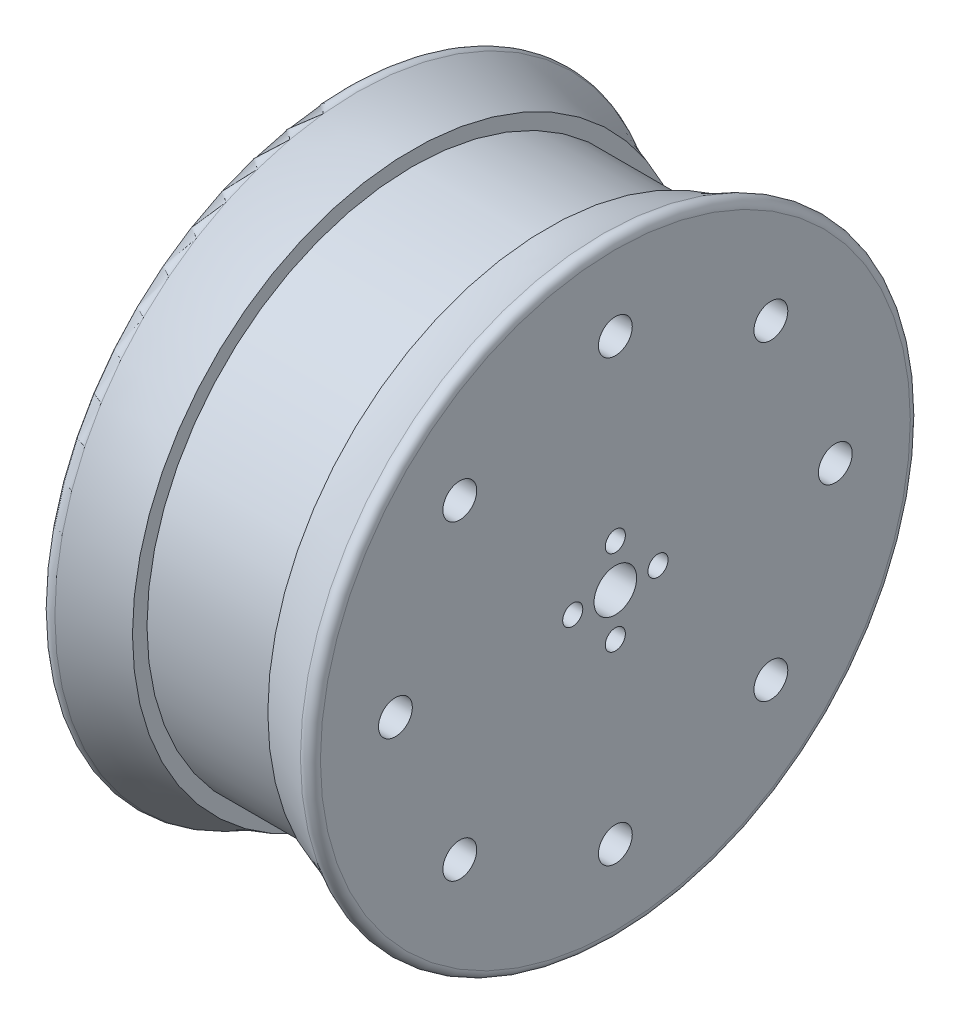
SolidWorks part; units mm, degrees
ref_plane "Front Plane" through (0, 0, 0) normal (0, 0, 1) x (1, 0, 0)
ref_plane "Top Plane" through (0, 0, 0) normal (0, 1, 0) x (1, 0, 0)
ref_plane "Right Plane" through (0, 0, 0) normal (1, 0, 0) x (0, 0, -1)
sketch "Wheel Arc" plane through (0, 0, 0) normal (0, 0, 1) x (1, 0, 0)
  line L0 (0, 0) -> (0, -98.425) construction
  line L1 (-25.4, 0) -> (25.4, 0)
  line L2 (-40.9053, 0) -> (38.2322, 0) construction
  line L3 (-25.4, 0) -> (-25.4, -58.1388)
  line L4 (25.4, 0) -> (25.4, -58.1388)
  line L5 (0, -50.8) -> (0, -49.8) construction
  line L6 (-12.7, -49.8) -> (12.7, -49.8)
  line L7 (-12.7, -49.8) -> (-12.7, -52.5246)
  line L8 (12.7, -49.8) -> (12.7, -52.5246)
  arc A0 (-25.4, -58.1388) -> (-12.7, -52.5246) centre (0, -98.425) cw
  arc A1 (12.7, -52.5246) -> (25.4, -58.1388) centre (0, -98.425) cw
  point P7 (0, 0)
  point P9 (0, 0)
  point P16 (0, -49.8)
  dimension "D6" = 47.625
  dimension "D2" = 50.8
  dimension "D4" = 1
  dimension "D5" = 25.4
  dimension "D1" = 47.625
  dimension "D3" = 50.8
ref_axis "Wheel Axis" through (-40.9053, 0, 0) along (1, 0, 0)
revolve "Wheel" add sketch "Wheel Arc" angle 360 about axis through (-40.9053, 0, 0) along (1, 0, 0)
sketch "Flower" plane through (25.4, 0, 0) normal (1, 0, 0) x (0, 0, -1)
  line L0 (0, 0) -> (0, 8) construction
  circle A0 centre (0, 0) radius 4
  circle A1 centre (0, 8) radius 1.885
  circle A2 centre (8, 0) radius 1.885
  circle A3 centre (0, -8) radius 1.885
  circle A4 centre (-8, 0) radius 1.885
  point P14 (0, 0)
  dimension "D1" = 4
extrude "Mounting" cut sketch "Flower" against normal through all
fillet "Fillet1" radius 1.5875 2 edges at (25.4, 0, 58.1388) (-25.4, 0, 58.1388)
sketch "Sketch1" plane through (25.4, 0, 0) normal (1, 0, 0) x (0, 0, -1)
  line L0 (0, 0) -> (0, 41.275) construction
  circle A0 centre (0, 41.275) radius 3.175
  circle A1 centre (29.1858, 29.1858) radius 3.175
  circle A2 centre (41.275, 0) radius 3.175
  circle A3 centre (29.1858, -29.1858) radius 3.175
  circle A4 centre (0, -41.275) radius 3.175
  circle A5 centre (-29.1858, -29.1858) radius 3.175
  circle A6 centre (-41.275, 0) radius 3.175
  circle A7 centre (-29.1858, 29.1858) radius 3.175
  point P21 (0, 0)
  dimension "D2" = 6.35
  dimension "D1" = 41.275
  dimension "D3" = 8
extrude "Mass_and_Balance" cut sketch "Sketch1" against normal through all
equation "\"BALL_DIAMETER\"= 3.75in"
equation "\"BALL_RADIUS\"= \"BALL_DIAMETER\" / 2"
equation "\"D1@Wheel Arc\"=\"BALL_RADIUS\""
equation "\"D6@Wheel Arc\"=\"BALL_RADIUS\""
